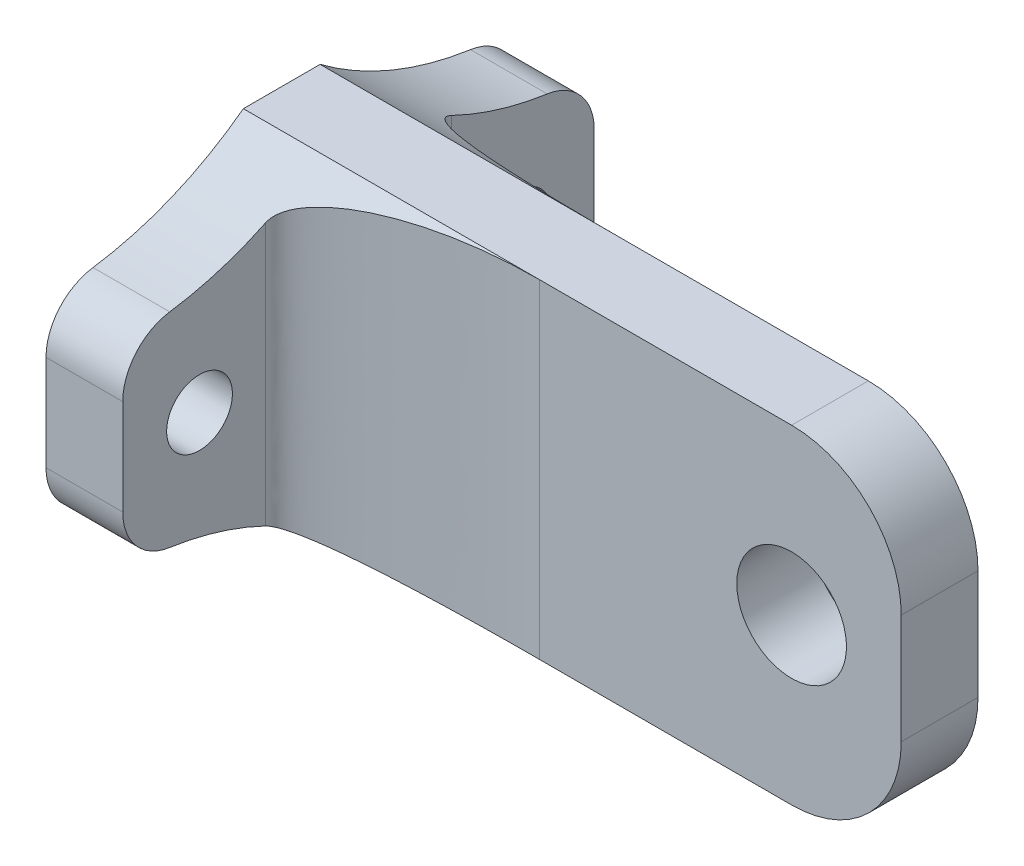
SolidWorks part; units mm, degrees
ref_plane "前视基准面" through (0, 0, 0) normal (0, 0, 1) x (1, 0, 0)
ref_plane "上视基准面" through (0, 0, 0) normal (0, 1, 0) x (1, 0, 0)
ref_plane "右视基准面" through (0, 0, 0) normal (1, 0, 0) x (0, 0, -1)
other "Configuration Table"
sketch "草图1" plane through (0, 0, 0) normal (0, 0, 1) x (1, 0, 0)
  line L1 (0, 0) -> (60, 0)
  line L2 (0, 0) -> (0, 30)
  line L3 (0, 30) -> (60, 30)
  line L4 (60, 0) -> (60, 30)
  dimension "D1" = 30
  dimension "D2" = 60
extrude "凸台-拉伸1" add sketch "草图1" along normal blind 7
sketch "草图2" plane through (0, 0, 0) normal (0, 0, -1) x (-1, 0, 0)
  line L0 (-60, 15) -> (0, 15) construction
  line L1 (-60, 0) -> (-60, 30) construction
  line L2 (0, 30) -> (0, 0) construction
  circle A0 centre (-50, 15) radius 5
  dimension "D1" = 10
  dimension "D2" = 50
extrude "切除-拉伸1" cut sketch "草图2" against normal up to next
sketch "草图3" plane through (0, 0, 7) normal (0, 0, 1) x (1, 0, 0)
  line L0 (0, 15) -> (20.808, 15) construction
  line L1 (0, 30) -> (0, 0) construction
  line L3 (0, 24) -> (7, 24)
  line L4 (0, 24) -> (0, 6)
  line L5 (0, 6) -> (7, 6)
  line L6 (7, 24) -> (7, 6)
  dimension "D1" = 18
  dimension "D2" = 9
  dimension "D3" = 7
extrude "凸台-拉伸2" add sketch "草图3" along normal blind 18
sketch "草图4" plane through (0, 0, 0) normal (0, 0, -1) x (-1, 0, 0)
  line L0 (0, 15) -> (-18.6209, 15) construction
  line L1 (0, 30) -> (0, 0) construction
  line L7 (0, 24) -> (-7, 24)
  line L8 (0, 24) -> (0, 6)
  line L9 (0, 6) -> (-7, 6)
  line L10 (-7, 24) -> (-7, 6)
  dimension "D1" = 18
  dimension "D2" = 9
  dimension "D3" = 7
extrude "凸台-拉伸3" add sketch "草图4" along normal blind 18
sketch "草图5" plane through (0, 0, 0) normal (-1, 0, 0) x (0, 0, 1)
  line L0 (-18, 15) -> (25, 15) construction
  line L1 (-18, 6) -> (-18, 24) construction
  line L2 (25, 24) -> (25, 6) construction
  circle A0 centre (-11, 15) radius 3
  circle A1 centre (18, 15) radius 3
  dimension "D1" = 6
  dimension "D2" = 6
  dimension "D3" = 7
  dimension "D4" = 7
extrude "切除-拉伸2" cut sketch "草图5" against normal up to next
fillet "圆角2" radius 20 2 edges at (7, 15, 7) (7, 15, 0)
fillet "圆角3" radius 30 4 edges
fillet "圆角4" radius 5 1 edges at (3.5, 24, 25)
fillet "圆角5" radius 5 2 edges at (3.5, 6, 25)
fillet "圆角6" radius 5 1 edges at (3.5, 6, -18)
fillet "圆角7" radius 5 2 edges at (3.5, 24, -18)
fillet "圆角8" radius 10 2 edges at (60, 0, 3.5) (60, 30, 3.5)
